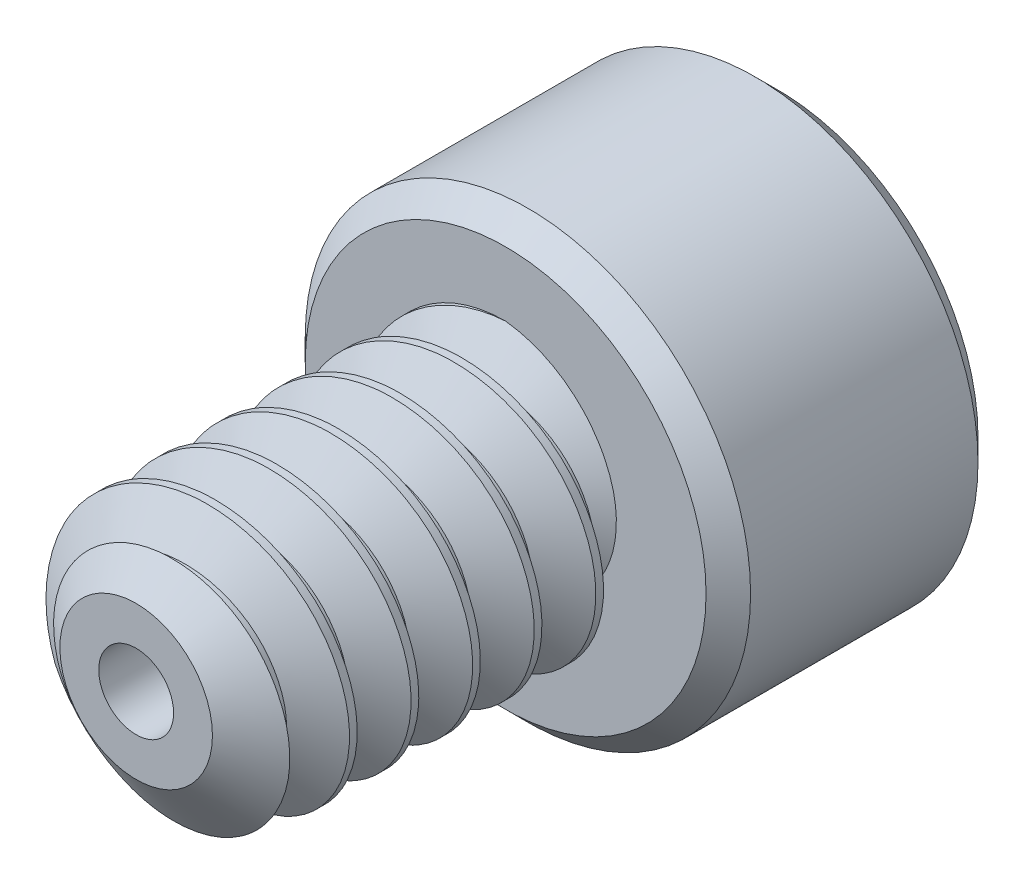
SolidWorks part; units mm, degrees
note: '?' marks a value the reader was unsure of.
ref_plane "Front Plane" through (0, 0, 0) normal (0, 0, 1) x (1, 0, 0)
ref_plane "Top Plane" through (0, 0, 0) normal (0, 1, 0) x (1, 0, 0)
ref_plane "Right Plane" through (0, 0, 0) normal (1, 0, 0) x (0, 0, -1)
sketch "Sketch1" plane through (0, 0, 0) normal (0, 0, 1) x (1, 0, 0)
  circle A0 centre (0, 0) radius 1.7526
  dimension "OD" = 3.5052
extrude "Extrude1" add sketch "Sketch1" against normal blind 4.7625
sketch "Sketch2" plane through (0, 0, 0) normal (0, 0, 1) x (1, 0, 0)
  circle A0 centre (0, 0) radius 1.7526 construction
  circle A1 centre (0, 0) radius 1.7526
curve "Helix/Spiral1" pitch 0.7937 height 5.5563 turns 7 parameters "pitch"=0.7937
sketch "Sketch3" plane through (0, 0, 0) normal (1, 0, 0) x (0, 0, -1)
  line L0 (-0.6945, 1.7526) -> (-0.3969, 1.237)
  line L1 (-0.3969, 1.237) -> (-0.2977, 1.237)
  line L2 (-0.2977, 1.237) -> (0, 1.7526)
  line L3 (-0.6945, 1.7526) -> (0, 1.7526)
  line L4 (-0.3473, 1.7526) -> (-0.3473, 1.237) construction
  line L5 (-0.5457, 1.4948) -> (-0.1488, 1.4948) construction
  line L6 (0, 1.7526) -> (0, -1.7526) construction
  dimension "D1" = 0.0992
  dimension "D2" = 0.3969
  dimension "D3" = 60
sweep "Cut-Sweep1" cut profiles "Sketch3" path "Helix/Spiral1"
sketch "Sketch4" plane through (0, 0, 0) normal (1, 0, 0) x (0, 0, -1)
  line L0 (0.5388, 1.7526) -> (0, 0.983)
  line L1 (0, 0.983) -> (0, 1.7526)
  line L2 (0.5388, 1.7526) -> (0, 1.7526)
  line L3 (-0.6945, 1.7526) -> (0, 1.7526) construction
  line L4 (0, 0) -> (7.0209, 0) construction
  dimension "D1" = 55
  dimension "D2" = 0.254
revolve "Cut-Revolve1" cut sketch "Sketch4" angle 360 about L4
sketch "Sketch6" plane through (0, 0, -4.7625) normal (0, 0, -1) x (-1, 0, 0)
  circle A0 centre (0, 0) radius 2.8702
  dimension "head dia" = 5.7404
extrude "Extrude2" add sketch "Sketch6" along normal blind 3.5052
sketch "Sketch7" plane through (0, 0, -8.2677) normal (0, 0, -1) x (-1, 0, 0)
  line L1 (0, 1.604) -> (-1.3891, 0.802)
  line L2 (-1.3891, 0.802) -> (-1.3891, -0.802)
  line L3 (-1.3891, -0.802) -> (0, -1.604)
  line L4 (0, -1.604) -> (1.3891, -0.802)
  line L5 (1.3891, -0.802) -> (1.3891, 0.802)
  line L6 (1.3891, 0.802) -> (0, 1.604)
  circle A0 centre (0, 0) radius 1.3891 construction
  dimension "hex dia" = 2.7781
extrude "Cut-Extrude1" cut sketch "Sketch7" against normal blind 2.0836
sketch "Sketch8" plane through (0, 0, -8.2677) normal (0, 0, -1) x (-1, 0, 0)
  circle A0 centre (0, 0) radius 1.604
extrude "Cut-Extrude2" cut sketch "Sketch8" against normal through all draft 45
chamfer "Chamfer1" distance 0.287 angle 45 2 edges at (-2.8702, 0, -8.2677) (-2.8702, 0, -4.7625)
sketch "Sketch10" plane through (0, 0, -4.7625) normal (0, 0, 1) x (1, 0, 0)
  circle A1 centre (0, 0) radius 1.7526
  circle A2 centre (0, 0) radius 1.7526
  dimension "D1" = 0
ref_plane "Plane1" through (0, 0, 0) normal (0, 0, 1) x (1, 0, 0)
extrude "partial thread" [suppressed] add sketch "Sketch10" along normal up to surface (4.7625 mm away) separate body
chamfer "Chamfer2" [suppressed] distance 0.0701 angle 45
combine bodies "Combine1" [suppressed] operation type? add bodies to combine 107 108
sketch "Sketch9" plane through (0, 0, 0) normal (1, 0, 0) x (0, 0, -1)
  line L0 (0, 1.7526) -> (0, -1.7526) construction
  line L1 (1.9844, 1.7526) -> (1.9844, -1.7526) construction
  dimension "D1" = 1.9844
sketch "Sketch11" plane through (0, 0, 0) normal (0, 0, 1) x (1, 0, 0)
  circle A0 centre (0, 0) radius 0.4826
  dimension "Vent Dia" = 0.9652
extrude "Cut-Extrude3" cut sketch "Sketch11" against normal through all
equation "\"D3@Helix/Spiral1\" = \"screw length@Extrude1\"+\"pitch@Helix/Spiral1\""
equation "\"D1@Sketch3\" = \"pitch@Helix/Spiral1\"*.125"
equation "\"D2@Sketch3\" = \"pitch@Helix/Spiral1\"*.5"
equation "\"D1@Cut-Extrude1\" = \"hex dia@Sketch7\"*.75"
equation "\"D1@Chamfer1\" = \"head dia@Sketch6\"*.05"
equation "\"D1@Sketch9\" = \"pitch@Helix/Spiral1\"*2.5"
equation "\"D1@Chamfer2\"=\"OD@Sketch1\"*.02"
